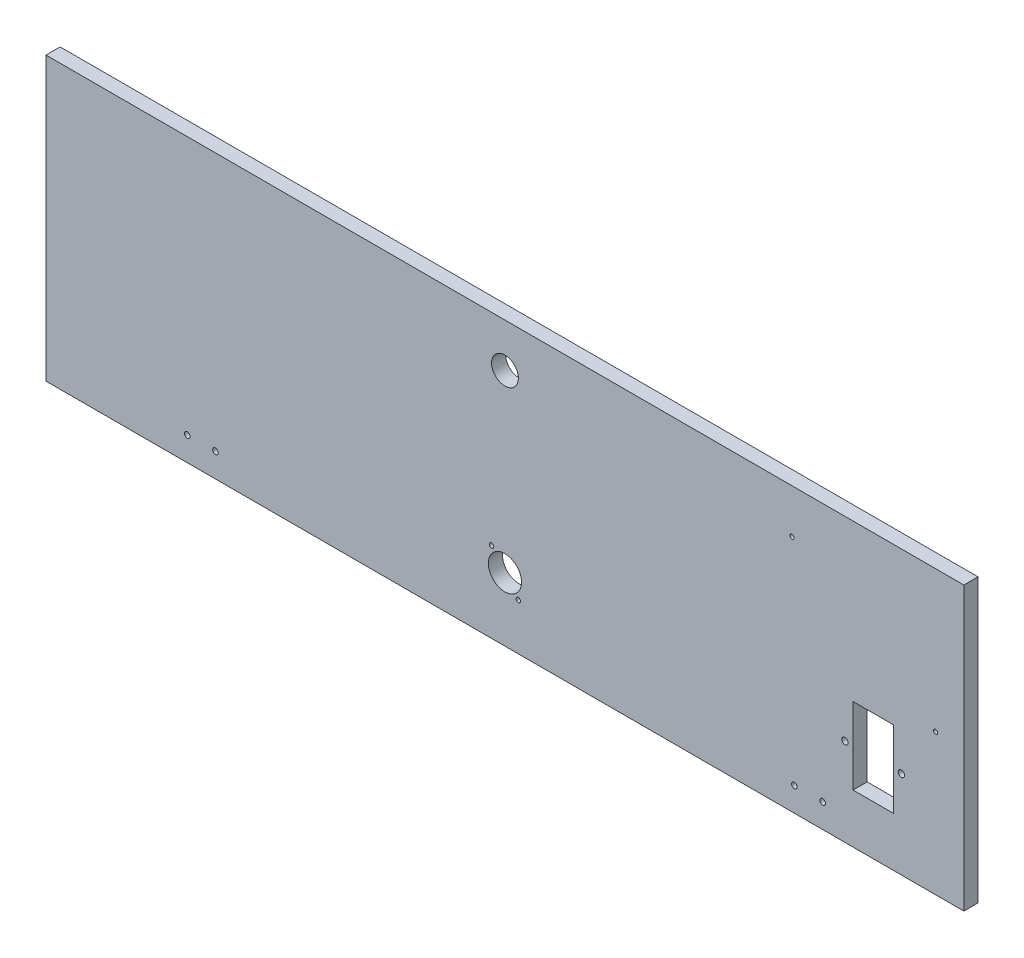
SolidWorks part; units mm, degrees
ref_plane "Plan de face" through (0, 0, 0) normal (0, 0, 1) x (1, 0, 0)
ref_plane "Plan de dessus" through (0, 0, 0) normal (0, 1, 0) x (1, 0, 0)
ref_plane "Plan de droite" through (0, 0, 0) normal (1, 0, 0) x (0, 0, -1)
sketch "Esquisse1" plane through (0, 0, 0) normal (0, 0, 1) x (1, 0, 0)
  line L1 (0, 0) -> (650, 0)
  line L2 (0, 0) -> (0, 200)
  line L3 (0, 200) -> (650, 200)
  line L4 (650, 0) -> (650, 200)
  dimension "D1" = 200
  dimension "D2" = 650
extrude "Boss.-Extru.1" add sketch "Esquisse1" along normal blind 10
sketch "Esquisse2" plane through (0, 0, 10) normal (0, 0, 1) x (1, 0, 0)
  line L4 (0, 200) -> (0, 0) construction
  line L5 (650, 0) -> (650, 200) construction
  line L6 (0, 0) -> (650, 0) construction
  circle A0 centre (100, 17) radius 2
  circle A1 centre (120, 17) radius 2
  circle A2 centre (530, 17) radius 2
  circle A3 centre (550, 17) radius 2
  dimension "D1" = 4
  dimension "D2" = 4
  dimension "D3" = 4
  dimension "D4" = 4
  dimension "D5" = 20
  dimension "D6" = 20
  dimension "D7" = 100
  dimension "D8" = 100
  dimension "D9" = 17
  dimension "D10" = 17
  dimension "D11" = 17
  dimension "D12" = 17
extrude "Enlèv. mat.-Extru.1" cut sketch "Esquisse2" against normal blind 10
sketch "Esquisse3" plane through (0, 0, 10) normal (0, 0, 1) x (1, 0, 0)
  line L0 (0, 0) -> (650, 0) construction
  line L1 (334.5004, 33.0006) -> (325, 45)
  line L2 (325, 45) -> (315.4996, 56.9994)
  line L3 (325, 45) -> (265.8175, 45)
  line L4 (325, 45) -> (364.3682, 45)
  line L5 (650, 0) -> (650, 200) construction
  line L6 (571.5, 35) -> (600, 35)
  line L7 (571.5, 35) -> (571.5, 89.3)
  line L8 (571.5, 89.3) -> (600, 89.3)
  line L9 (600, 35) -> (600, 89.3)
  circle A0 centre (325, 45) radius 11.75
  circle A1 centre (315.4996, 56.9994) radius 1.6
  circle A2 centre (334.5004, 33.0006) radius 1.6
  circle A3 centre (565.75, 62.15) radius 2.25
  circle A4 centre (605.75, 62.15) radius 2.25
  point P4 (325, 0)
  point P19 (585.75, 89.3)
  point P20 (571.5, 62.15)
  dimension "D1" = 23.5
  dimension "D4" = 3.2
  dimension "D5" = 3.2
  dimension "D14" = 4.5
  dimension "D15" = 4.5
  dimension "D2" = 0
  dimension "D3" = 45
  dimension "D6" = 30.61
  dimension "D7" = 15.305
  dimension "D8" = 51.63
  dimension "D9" = 180
  dimension "D10" = 51.63
  dimension "D11" = 15.305
  dimension "D12" = 28.5
  dimension "D13" = 54.3
  dimension "D16" = 40
  dimension "D17" = 20
  dimension "D18" = 0
  dimension "D19" = 35
  dimension "D20" = 50
  dimension "D21" = 20
extrude "Enlèv. mat.-Extru.2" cut sketch "Esquisse3" against normal blind 10 contours L3 A0 L1 | L4 A0 L2 | L1 A0 L4 | L2 A0 L3 | A1 | A2 | L6 L9 L8 L7 | A3 | A4 region at (314.1, 57.6764, 10) region at (322.2589, 39.3335, 10) region at (331.8154, 41.7031, 10) region at (335.1774, 34.4002, 10) region at (318.1846, 48.2969, 10) region at (327.7411, 50.6665, 10) region at (585.75, 62.15, 10)
sketch "Esquisse4" plane through (0, 0, 10) normal (0, 0, 1) x (1, 0, 0)
  line L0 (650, 200) -> (0, 200) construction
  circle A0 centre (325, 169) radius 9.5
  point P4 (325, 200)
  dimension "D1" = 19
  dimension "D3" = 31
  dimension "D2" = 0
extrude "Enlèv. mat.-Extru.3" cut sketch "Esquisse4" against normal blind 10
sketch "Esquisse5" plane through (0, 0, 0) normal (0, 0, 1) x (1, 0, 0)
  line L0 (650, 200) -> (0, 200) construction
  line L1 (650, 200) -> (0, 200) construction
  line L2 (0, 200) -> (0, 0) construction
  line L3 (650, 0) -> (650, 200) construction
  circle A0 centre (341, 169) radius 1
  circle A1 centre (309, 169) radius 1
  circle A2 centre (125, 193) radius 1
  circle A3 centre (105, 193) radius 1
  circle A4 centre (545, 193) radius 1
  circle A5 centre (525, 193) radius 1
  point P6 (325, 200)
  dimension "D2" = 2
  dimension "D3" = 2
  dimension "D7" = 2
  dimension "D8" = 2
  dimension "D9" = 2
  dimension "D10" = 2
  dimension "D1" = 32
  dimension "D4" = 16
  dimension "D5" = 31
  dimension "D6" = 31
  dimension "D11" = 20
  dimension "D12" = 7
  dimension "D13" = 7
  dimension "D14" = 105
  dimension "D15" = 7
  dimension "D16" = 7
  dimension "D17" = 20
  dimension "D18" = 105
extrude "Enlèv. mat.-Extru.4" cut sketch "Esquisse5" along normal blind 2
sketch "Esquisse6" plane through (0, 0, 0) normal (0, 0, -1) x (-1, 0, 0)
  line L0 (-650, 0) -> (-650, 200) construction
  line L1 (-650, 200) -> (0, 200) construction
  circle A0 centre (-528.25, 168.75) radius 1.5
  circle A1 centre (-630, 100) radius 1.5
  point P6 (-650, 100)
  dimension "D1" = 3
  dimension "D2" = 3
  dimension "D3" = 20
  dimension "D4" = 100
  dimension "D5" = 101.75
  dimension "D6" = 68.75
extrude "Enlèv. mat.-Extru.5" cut sketch "Esquisse6" against normal blind 10
